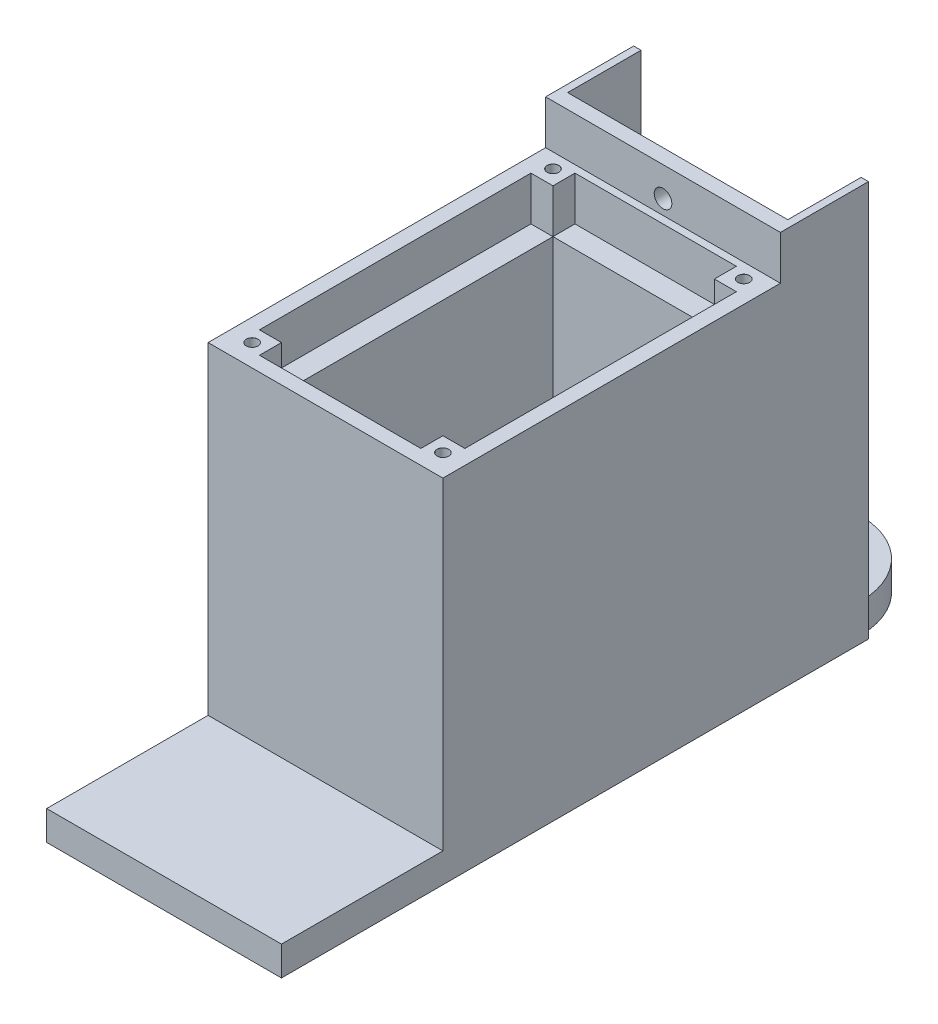
SolidWorks part; units mm, degrees
ref_plane "Front Plane" through (0, 0, 0) normal (0, 0, 1) x (1, 0, 0)
ref_plane "Top Plane" through (0, 0, 0) normal (0, 1, 0) x (1, 0, 0)
ref_plane "Right Plane" through (0, 0, 0) normal (1, 0, 0) x (0, 0, -1)
sketch "Sketch2" plane through (0, 0, 0) normal (0, 1, 0) x (1, 0, 0)
  line L0 (155, 400) -> (160, 400)
  line L1 (0, 0) -> (160, 0)
  line L2 (0, 0) -> (0, 400)
  line L3 (0, 400) -> (5, 400)
  line L4 (160, 0) -> (160, 400)
  line L6 (5, 400) -> (5, 450)
  line L7 (5, 450) -> (155, 450)
  line L8 (155, 400) -> (155, 450)
  dimension "D1" = 160
  dimension "D2" = 400
  dimension "D3" = 5
  dimension "D4" = 5
  dimension "D5" = 50
extrude "Boss-Extrude1" add sketch "Sketch2" along normal blind 20
fillet "Fillet1" radius 50 2 edges at (155, 10, -450) (5, 10, -450)
sketch "Sketch3" plane through (0, 20, 0) normal (0, 1, 0) x (1, 0, 0)
  line L0 (0, 400) -> (0, 340)
  line L1 (0, 400) -> (0, 0) construction
  line L2 (0, 340) -> (160, 340)
  line L3 (160, 0) -> (160, 400) construction
  line L4 (160, 340) -> (160, 400)
  line L5 (160, 400) -> (155, 400)
  line L6 (5, 400) -> (0, 400) construction
  line L7 (155, 400) -> (155, 350)
  line L8 (155, 350) -> (5, 350)
  line L9 (5, 350) -> (5, 400)
  line L10 (5, 400) -> (0, 400)
  dimension "D1" = 5
  dimension "D2" = 5
  dimension "D3" = 50
  dimension "D4" = 10
  dimension "D5" = 150
extrude "Boss-Extrude2" add sketch "Sketch3" along normal blind 250
sketch "Sketch4" plane through (0, 0, -340) normal (0, 0, 1) x (1, 0, 0)
  line L0 (0, 270) -> (160, 270) construction
  line L1 (0, 270) -> (0, 20) construction
  circle A0 centre (80, 250) radius 6
  dimension "D1" = 12
  dimension "D2" = 20
  dimension "D3" = 80
extrude "Cut-Extrude1" cut sketch "Sketch4" against normal blind 10
sketch "Sketch5" plane through (0, 0, -350) normal (0, 0, -1) x (-1, 0, 0)
  circle A0 centre (-80, 250) radius 6
  circle A1 centre (-80, 250) radius 8
  dimension "D1" = 16
  dimension "D2" = 12
extrude "Boss-Extrude3" add sketch "Sketch5" along normal blind 12 contours A1 | A0
fillet "Fillet2" radius 1 2 edges at (74, 250, -362) (72, 250, -362)
sketch "Sketch6" plane through (0, 20, 0) normal (0, 1, 0) x (1, 0, 0)
  line L0 (155, 350) -> (5, 350) construction
  line L1 (30, 350) -> (45, 350)
  line L2 (30, 350) -> (30, 410)
  line L3 (30, 410) -> (45, 410)
  line L4 (45, 350) -> (45, 410)
  line L5 (5, 350) -> (5, 400) construction
  line L6 (115, 350) -> (130, 350)
  line L7 (115, 350) -> (115, 410)
  line L8 (115, 410) -> (130, 410)
  line L9 (130, 350) -> (130, 410)
  line L10 (155, 400) -> (155, 350) construction
  dimension "D1" = 25
  dimension "D2" = 25
  dimension "D3" = 15
  dimension "D4" = 15
  dimension "D5" = 60
extrude "Boss-Extrude4" add sketch "Sketch6" along normal blind 6
sketch "Sketch7" plane through (0, 20, 0) normal (0, 1, 0) x (1, 0, 0)
  line L0 (0, 340) -> (0, 0) construction
  line L1 (55, 220) -> (105, 220)
  line L2 (55, 220) -> (55, 130)
  line L3 (55, 130) -> (105, 130)
  line L4 (105, 220) -> (105, 130)
  line L6 (0, 340) -> (160, 340) construction
  dimension "D1" = 50
  dimension "D2" = 55
  dimension "D3" = 90
  dimension "D4" = 120
extrude "Boss-Extrude5" add sketch "Sketch7" along normal blind 30
sketch "Sketch8" plane through (55, 0, 0) normal (-1, 0, 0) x (0, 0, 1)
  line L0 (-220, 50) -> (-130, 50) construction
  line L1 (-220, 50) -> (-220, 20) construction
  circle A0 centre (-195, 41) radius 3.3
  dimension "D1" = 6.6
  dimension "D2" = 9
  dimension "D3" = 25
extrude "Cut-Extrude2" cut sketch "Sketch8" against normal up to next
sketch "Sketch9" plane through (0, 50, 0) normal (0, 1, 0) x (1, 0, 0)
  line L0 (80, 220) -> (80, 130) construction
  line L1 (71, 186) -> (89, 186)
  line L2 (71, 186) -> (71, 204)
  line L3 (71, 204) -> (89, 204)
  line L4 (89, 186) -> (89, 204)
  line L5 (71, 186) -> (89, 204) construction
  line L6 (71, 204) -> (89, 186) construction
  line L7 (105, 220) -> (55, 220) construction
  line L8 (55, 130) -> (105, 130) construction
  line L9 (55, 175) -> (105, 175) construction
  line L10 (55, 220) -> (55, 130) construction
  line L11 (105, 130) -> (105, 220) construction
  point P0 (80, 195)
  dimension "D1" = 18
  dimension "D2" = 25
extrude "Cut-Extrude3" cut sketch "Sketch9" against normal blind 20
sketch "Sketch10" plane through (0, 50, 0) normal (0, 1, 0) x (1, 0, 0)
  line L0 (55, 130) -> (105, 130)
  line L1 (105, 130) -> (105, 220)
  line L2 (105, 220) -> (55, 220)
  line L3 (55, 220) -> (55, 130)
  line L5 (60, 214) -> (100, 214)
  line L6 (60, 214) -> (60, 159)
  line L8 (100, 214) -> (100, 159)
  arc A0 (60, 159) -> (100, 159) centre (80, 159) ccw
  dimension "D1" = 5
  dimension "D2" = 5
  dimension "D4" = 6
extrude "Boss-Extrude6" add sketch "Sketch10" along normal blind 20
chamfer "Chamfer1" distance 10 distance2 13 1 edges at (60, 60, -214) first distance on face at (60, 60, -186.5)
chamfer "Chamfer2" distance 13 distance2 10 1 edges at (100, 60, -214) first distance on face at (86.5, 60, -214)
fillet "Fillet3" radius 2 4 edges at (100, 60, -204) (87, 60, -214) (73, 60, -214) (60, 60, -204)
sketch "Sketch11" plane through (0, 20, 0) normal (0, 1, 0) x (1, 0, 0)
  line L0 (0, 340) -> (0, 110)
  line L1 (0, 110) -> (160, 110)
  line L2 (160, 110) -> (160, 340)
  line L3 (160, 340) -> (155, 340)
  line L4 (0, 340) -> (160, 340) construction
  line L5 (155, 340) -> (155, 115)
  line L6 (155, 115) -> (5, 115)
  line L7 (5, 115) -> (5, 340)
  line L8 (5, 340) -> (0, 340)
  line L9 (0, 0) -> (160, 0) construction
  dimension "D1" = 5
  dimension "D2" = 5
  dimension "D3" = 5
  dimension "D4" = 110
extrude "Boss-Extrude7" add sketch "Sketch11" along normal blind 220
sketch "Sketch12" plane through (0, 20, 0) normal (0, 1, 0) x (1, 0, 0)
  line L1 (5, 340) -> (25, 340)
  line L2 (5, 340) -> (5, 320)
  line L3 (5, 320) -> (25, 320)
  line L4 (25, 340) -> (25, 320)
  line L5 (155, 340) -> (135, 340)
  line L6 (155, 340) -> (155, 320)
  line L7 (155, 320) -> (135, 320)
  line L8 (135, 340) -> (135, 320)
  line L9 (5, 115) -> (25, 115)
  line L10 (5, 115) -> (5, 135)
  line L11 (5, 135) -> (25, 135)
  line L12 (25, 115) -> (25, 135)
  line L13 (155, 115) -> (135, 115)
  line L14 (155, 115) -> (155, 135)
  line L15 (155, 135) -> (135, 135)
  line L16 (135, 115) -> (135, 135)
  line L17 (5, 320) -> (10, 320)
  line L18 (5, 320) -> (5, 135)
  line L19 (5, 135) -> (10, 135)
  line L20 (10, 320) -> (10, 135)
  line L21 (25, 115) -> (135, 115)
  line L22 (25, 115) -> (25, 120)
  line L23 (25, 120) -> (135, 120)
  line L24 (135, 115) -> (135, 120)
  line L25 (155, 135) -> (150, 135)
  line L26 (155, 135) -> (155, 320)
  line L27 (155, 320) -> (150, 320)
  line L28 (150, 135) -> (150, 320)
  line L29 (135, 340) -> (25, 340)
  line L30 (135, 340) -> (135, 335)
  line L31 (135, 335) -> (25, 335)
  line L32 (25, 340) -> (25, 335)
  line M12 (155, 115) -> (155, 340)
  line M13 (155, 340) -> (5, 340)
  line M14 (5, 340) -> (5, 115)
  line M15 (5, 115) -> (155, 115)
  dimension "D1" = 20
  dimension "D2" = 20
  dimension "D3" = 20
  dimension "D4" = 20
  dimension "D5" = 20
  dimension "D6" = 20
  dimension "D7" = 20
  dimension "D8" = 20
  dimension "D9" = 5
  dimension "D10" = 5
  dimension "D11" = 5
  dimension "D12" = 5
extrude "Boss-Extrude8" add sketch "Sketch12" along normal blind 220 contours L23 L12 L16 M15 | L12 L11 M15 M14 | L20 L3 L11 M14 | L4 L3 M13 M14 | L31 L8 L4 M13 | L8 L7 M13 M12 | L28 L15 L7 M12 | L16 L15 M15 M12 region at (15, 20, -330) region at (80, 20, -337.5) region at (7.5, 20, -227.5) region at (145, 20, -330) region at (15, 20, -125) region at (152.5, 20, -227.5) region at (80, 20, -117.5) region at (145, 20, -125)
sketch "Sketch14" plane through (0, 240, 0) normal (0, 1, 0) x (1, 0, 0)
  line L2 (80, 340) -> (80, 115) construction
  line L3 (0, 340) -> (160, 340) construction
  line L10 (5, 227.5) -> (155, 227.5) construction
  point P0 (15, 330)
  point P31 (145, 330)
  point P32 (145, 125)
  point P33 (15, 125)
hole_wizard "Ø8.0mm Dowel Hole1" positions "Sketch14" profile "Sketch15" hole size "Ø8.0" standard "ANSI Metric"
sketch "Sketch15" plane through (15, 240, -330) normal (1, 0, 0) x (0, 0, 1)
  line L0 (0, 0) -> (0, 18.4034)
  line L1 (0, 18.4034) -> (4, 16)
  line L2 (4, 16) -> (4, 0.025)
  line L3 (4, 0.025) -> (4.025, 0)
  line L5 (4.025, 0) -> (0, 0)
  line L6 (-4, 0.025) -> (-4.025, 0) construction
  line L10 (0, 18.4034) -> (-4, 16) construction
  line L11 (0, -6.35) -> (0, 107.95) construction
  dimension "Hole Dia." = 8
  dimension "Hole Depth" = 16
  dimension "Near C'Sink Dia." = 8.05
  dimension "Near C'Sink Angle" = 90
  dimension "Drill Angle" = 118
sketch "Sketch16" plane through (0, 20, 0) normal (0, 1, 0) x (1, 0, 0)
  line L0 (25, 335) -> (135, 335)
  line L1 (135, 335) -> (25, 335) construction
  line L2 (135, 335) -> (135, 320)
  line L3 (135, 320) -> (150, 320)
  line L4 (150, 320) -> (150, 135)
  line L5 (150, 135) -> (135, 135)
  line L6 (135, 135) -> (135, 120)
  line L7 (135, 120) -> (25, 120)
  line L8 (25, 120) -> (25, 135)
  line L9 (25, 135) -> (10, 135)
  line L10 (10, 135) -> (10, 320)
  line L11 (10, 320) -> (25, 320) construction
  line L12 (10, 320) -> (10, 135) construction
  line L13 (10, 320) -> (25, 320)
  line L14 (25, 335) -> (25, 320) construction
  line L15 (25, 320) -> (25, 335)
  line L16 (25, 320) -> (135, 320)
  line L17 (135, 320) -> (135, 130)
  line L18 (135, 130) -> (25, 130)
  line L19 (25, 130) -> (25, 320)
  line M17 (135, 335) -> (25, 335)
  line M18 (25, 335) -> (25, 320)
  line M19 (25, 320) -> (10, 320)
  line M20 (10, 320) -> (10, 135)
  line M21 (10, 135) -> (25, 135)
  line M23 (25, 120) -> (135, 120)
  line M24 (135, 120) -> (135, 135)
  line M25 (135, 135) -> (150, 135)
  line M26 (150, 135) -> (150, 320)
  line M27 (150, 320) -> (135, 320)
  line M28 (135, 320) -> (135, 335)
  line M32 (105, 130) -> (55, 130)
  dimension "D1" = 15
  dimension "D2" = 15
  dimension "D3" = 10
extrude "Boss-Extrude9" add sketch "Sketch16" along normal blind 190 contours L19 M21 M19 M20 | L16 M18 M28 M17 | L17 M27 M25 M26 | L18 L8 M24 M32 M23 region at (80, 20, -327.5) region at (17.5, 20, -227.5) region at (142.5, 20, -227.5) region at (80, 20, -125)
